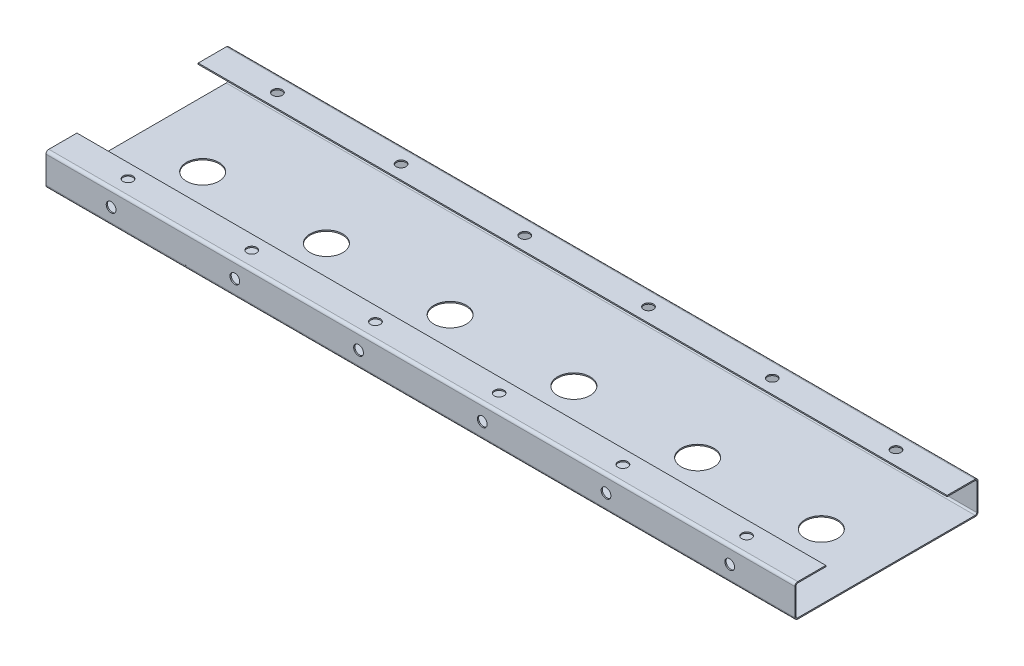
SolidWorks part; units mm, degrees
note: The reader was unsure of these and kept them because the rebuilt part matched: flange length of "Edge-Flange1", "Edge-Flange2".
material "Galvanized Steel"
ref_plane "Front Plane" through (0, 0, 0) normal (0, 0, 1) x (1, 0, 0)
ref_plane "Top Plane" through (0, 0, 0) normal (0, 1, 0) x (1, 0, 0)
ref_plane "Right Plane" through (0, 0, 0) normal (1, 0, 0) x (0, 0, -1)
sketch "Sketch1" plane through (0, 0, 0) normal (0, 1, 0) x (1, 0, 0)
  line L1 (-460, -112.5) -> (460, -112.5)
  line L2 (-460, -112.5) -> (-460, 112.5)
  line L3 (-460, 112.5) -> (460, 112.5)
  line L4 (460, -112.5) -> (460, 112.5)
  line L5 (-460, -112.5) -> (460, 112.5) construction
  line L6 (-460, 112.5) -> (460, -112.5) construction
  point P0 (0, 0)
base flange "Base-Flange1" sketch "Sketch1" thickness 1.5 reverse thickness direction no parameters "D1"=2
edge flange "Edge-Flange1" sketch "Sketch10" flange profiles "Sketch10", "Sketch11" flange angle 90 flange length 40 flange position material inside bend radius 2 thickness 1.5 relief rectangular parameters "D6"=10, "D8"=1
sketch "Sketch10" plane through (0, 0, 112.5) normal (0, 0, 1) x (1, 0, 0)
  line L0 (-460, 0) -> (460, 0) construction
  line L1 (-460, 0) -> (460, 0)
  line L2 (-460, 0) -> (-460, 38.5)
  line L3 (-460, 38.5) -> (460, 38.5)
  line L4 (460, 38.5) -> (460, 0)
sketch "Sketch11" plane through (0, 0, -112.5) normal (0, 0, -1) x (-1, 0, 0)
  line L0 (-460, 0) -> (460, 0) construction
  line L1 (-460, 0) -> (460, 0)
  line L2 (-460, 0) -> (-460, 38.5)
  line L3 (-460, 38.5) -> (460, 38.5)
  line L4 (460, 38.5) -> (460, 0)
bend "EdgeBend1" bend radius 2 bend angle 90 parameters "D5"=1
bend "EdgeBend2" bend radius 2 bend angle 90 parameters "D5"=2
edge flange "Edge-Flange2" sketch "Sketch16" flange profiles "Sketch16", "Sketch17" flange angle 90 flange length 38 flange position material inside bend radius 2 thickness 1.5 relief rectangular parameters "D6"=10, "D8"=1
sketch "Sketch16" plane through (0, 38.5, 111) normal (0, 1, 0) x (1, 0, 0)
  line L2 (-460, 0) -> (-460, 36.5)
  line L3 (-460, 36.5) -> (460, 36.5)
  line L4 (460, 36.5) -> (460, 0)
  line L7 (460, 0) -> (-460, 0) construction
  line L8 (460, 0) -> (-460, 0)
sketch "Sketch17" plane through (0, 38.5, -111) normal (0, 1, 0) x (-1, 0, 0)
  line L0 (460, 0) -> (-460, 0) construction
  line L1 (460, 0) -> (-460, 0)
  line L2 (-460, 0) -> (-460, 36.5)
  line L3 (-460, 36.5) -> (460, 36.5)
  line L4 (460, 36.5) -> (460, 0)
bend "EdgeBend3" bend radius 2 bend angle 90 parameters "D5"=3
bend "EdgeBend4" bend radius 2 bend angle 90 parameters "D5"=4
sketch "Sketch18" plane through (0, 0, 112.5) normal (0, 0, 1) x (1, 0, 0)
  line L0 (-460, 35) -> (-460, 2) construction
  circle A0 centre (380, 18.5) radius 6
  circle A1 centre (228, 18.5) radius 6
  circle A2 centre (76, 18.5) radius 6
  circle A3 centre (-76, 18.5) radius 6
  circle A4 centre (-228, 18.5) radius 6
  circle A5 centre (-380, 18.5) radius 6
  dimension "D1" = 6
  dimension "D2" = 80
extrude "Cut-Extrude1" cut sketch "Sketch18" against normal blind 280
sketch "Sketch19" plane through (0, 38.5, 0) normal (0, 1, 0) x (1, 0, 0)
  circle A0 centre (-380, -91.75) radius 6
  circle A1 centre (-228, -91.75) radius 6
  circle A2 centre (-76, -91.75) radius 6
  circle A3 centre (76, -91.75) radius 6
  circle A4 centre (228, -91.75) radius 6
  circle A5 centre (380, -91.75) radius 6
  circle A6 centre (380, 91.75) radius 6
  circle A7 centre (228, 91.75) radius 6
  circle A8 centre (76, 91.75) radius 6
  circle A9 centre (-76, 91.75) radius 6
  circle A10 centre (-228, 91.75) radius 6
  circle A11 centre (-380, 91.75) radius 6
  dimension "D1" = 6
extrude "Cut-Extrude2" cut sketch "Sketch19" against normal blind 5
sketch "Sketch20" plane through (0, 0, 0) normal (0, 1, 0) x (1, 0, 0)
  circle A0 centre (-380, 0) radius 20
  circle A1 centre (-228, 0) radius 20
  circle A2 centre (-76, 0) radius 20
  circle A3 centre (76, 0) radius 20
  circle A4 centre (228, 0) radius 20
  circle A5 centre (380, 0) radius 20
  dimension "D1" = 6
extrude "Cut-Extrude3" cut sketch "Sketch20" against normal blind 65
sketch "Bend-Lines1" [suppressed] plane through (0, 0, 0) normal (0, 1, 0) x (1, 0, 0)
sketch "Bounding-Box1" [suppressed] plane through (0, 0, 0) normal (0, 1, 0) x (1, 0, 0)
sheet metal parameters "Sheet-Metal1" thickness 1.5 parameters "D1"=2
flat pattern "Flat-Pattern1" [suppressed]
sketch "Bend-Lines2" plane through (0, 0, 0) normal (0, 1, 0) x (1, 0, 0)
sketch3d "Bounding-Box2" [suppressed]
  line L0 (-456, 112.5, 0) -> (456, 112.5, 0) construction
  line L1 (-456, -112.5, 0) -> (456, -112.5, 0) construction
  line L2 (-456, 112.5, 0) -> (-456, -112.5, 0) construction
  line L3 (456, 112.5, 0) -> (456, -112.5, 0) construction
sheet metal parameters "Sheet-Metal2" thickness 1.5 parameters "D1"=2
flat pattern "Flat-Pattern1"
sketch "Bend-Lines2" plane through (0, 0, 0) normal (0, 1, 0) x (1, 0, 0)
  line L0 (456, 111.1598) -> (-456, 111.1598) construction
  line L1 (-456, -111.1598) -> (456, -111.1598) construction
  line L2 (456, 111.1598) -> (-456, 111.1598) construction
  line L3 (-456, -111.1598) -> (456, -111.1598) construction
sketch3d "Bounding-Box2" [suppressed]
  line L0 (456, 149.8197, 0) -> (-456, 149.8197, 0) construction
  line L1 (456, -149.8197, 0) -> (-456, -149.8197, 0) construction
  line L2 (456, 149.8197, 0) -> (456, -149.8197, 0) construction
  line L3 (-456, 149.8197, 0) -> (-456, -149.8197, 0) construction
bend of the flat pattern "Flatten-<EdgeBend1>1"
bend of the flat pattern "Flatten-<EdgeBend2>1"
sheet metal parameters "Sheet-Metal3" thickness 1.5 parameters "D1"=2
flat pattern "Flat-Pattern1"
sketch "Bend-Lines2" plane through (0, 0, 0) normal (0, 1, 0) x (1, 0, 0)
  line L0 (456, 111.1598) -> (-456, 111.1598) construction
  line L1 (-456, -111.1598) -> (456, -111.1598) construction
  line L2 (456, 111.1598) -> (-456, 111.1598) construction
  line L3 (-456, -111.1598) -> (456, -111.1598) construction
  line L4 (456, 148.4795) -> (-456, 148.4795) construction
  line L5 (-456, -148.4795) -> (456, -148.4795) construction
  line L6 (456, 148.4795) -> (-456, 148.4795) construction
  line L7 (-456, -148.4795) -> (456, -148.4795) construction
sketch3d "Bounding-Box2" [suppressed]
  line L0 (456, 185.1394, 0) -> (-456, 185.1394, 0) construction
  line L1 (456, -185.1394, 0) -> (-456, -185.1394, 0) construction
  line L2 (456, 185.1394, 0) -> (456, -185.1394, 0) construction
  line L3 (-456, 185.1394, 0) -> (-456, -185.1394, 0) construction
bend of the flat pattern "Flatten-<EdgeBend1>1"
bend of the flat pattern "Flatten-<EdgeBend2>1"
bend of the flat pattern "Flatten-<EdgeBend3>1"
bend of the flat pattern "Flatten-<EdgeBend4>1"
sheet metal parameters "Sheet-Metal4" thickness 1.5 parameters "D1"=2
flat pattern "Flat-Pattern1"
sketch "Bend-Lines2" plane through (0, 0, 0) normal (0, 1, 0) x (1, 0, 0)
  line L0 (456, 111.1598) -> (-456, 111.1598) construction
  line L1 (-456, -111.1598) -> (456, -111.1598) construction
  line L2 (456, 111.1598) -> (-456, 111.1598) construction
  line L3 (-456, -111.1598) -> (456, -111.1598) construction
  line L4 (456, 148.4795) -> (-456, 148.4795) construction
  line L5 (-456, -148.4795) -> (456, -148.4795) construction
  line L6 (456, 148.4795) -> (-456, 148.4795) construction
  line L7 (-456, -148.4795) -> (456, -148.4795) construction
sketch3d "Bounding-Box2" [suppressed]
  line L0 (456, 185.1394, 0) -> (-456, 185.1394, 0) construction
  line L1 (456, -185.1394, 0) -> (-456, -185.1394, 0) construction
  line L2 (456, 185.1394, 0) -> (456, -185.1394, 0) construction
  line L3 (-456, 185.1394, 0) -> (-456, -185.1394, 0) construction
bend of the flat pattern "Flatten-<EdgeBend1>1"
bend of the flat pattern "Flatten-<EdgeBend2>1"
bend of the flat pattern "Flatten-<EdgeBend3>1"
bend of the flat pattern "Flatten-<EdgeBend4>1"
sheet metal parameters "Sheet-Metal5" thickness 1.5 parameters "D1"=2
flat pattern "Flat-Pattern1"
sketch "Bend-Lines2" plane through (0, 0, 0) normal (0, 1, 0) x (1, 0, 0)
  line L0 (456, 111.1598) -> (-456, 111.1598) construction
  line L1 (-456, -111.1598) -> (456, -111.1598) construction
  line L2 (456, 111.1598) -> (-456, 111.1598) construction
  line L3 (-456, -111.1598) -> (456, -111.1598) construction
  line L4 (456, 148.4795) -> (-456, 148.4795) construction
  line L5 (-456, -148.4795) -> (456, -148.4795) construction
  line L6 (456, 148.4795) -> (-456, 148.4795) construction
  line L7 (-456, -148.4795) -> (456, -148.4795) construction
sketch3d "Bounding-Box2" [suppressed]
  line L0 (456, 185.1394, 0) -> (-456, 185.1394, 0) construction
  line L1 (456, -185.1394, 0) -> (-456, -185.1394, 0) construction
  line L2 (456, 185.1394, 0) -> (456, -185.1394, 0) construction
  line L3 (-456, 185.1394, 0) -> (-456, -185.1394, 0) construction
bend of the flat pattern "Flatten-<EdgeBend1>1"
bend of the flat pattern "Flatten-<EdgeBend2>1"
bend of the flat pattern "Flatten-<EdgeBend3>1"
bend of the flat pattern "Flatten-<EdgeBend4>1"
sheet metal parameters "Sheet-Metal6" thickness 1.5 parameters "D1"=2
flat pattern "Flat-Pattern1"
sketch "Bend-Lines2" plane through (0, 0, 0) normal (0, 1, 0) x (1, 0, 0)
  line L0 (460, 111.1598) -> (-460, 111.1598) construction
  line L1 (-460, -111.1598) -> (460, -111.1598) construction
  line L2 (460, 111.1598) -> (-460, 111.1598) construction
  line L3 (-460, -111.1598) -> (460, -111.1598) construction
  line L4 (460, 148.4795) -> (-460, 148.4795) construction
  line L5 (-460, -148.4795) -> (460, -148.4795) construction
  line L6 (460, 148.4795) -> (-460, 148.4795) construction
  line L7 (-460, -148.4795) -> (460, -148.4795) construction
sketch3d "Bounding-Box2" [suppressed]
  line L0 (460, 185.1394, 0) -> (-460, 185.1394, 0) construction
  line L1 (460, -185.1394, 0) -> (-460, -185.1394, 0) construction
  line L2 (460, 185.1394, 0) -> (460, -185.1394, 0) construction
  line L3 (-460, 185.1394, 0) -> (-460, -185.1394, 0) construction
bend of the flat pattern "Flatten-<EdgeBend1>1"
bend of the flat pattern "Flatten-<EdgeBend2>1"
bend of the flat pattern "Flatten-<EdgeBend3>1"
bend of the flat pattern "Flatten-<EdgeBend4>1"
